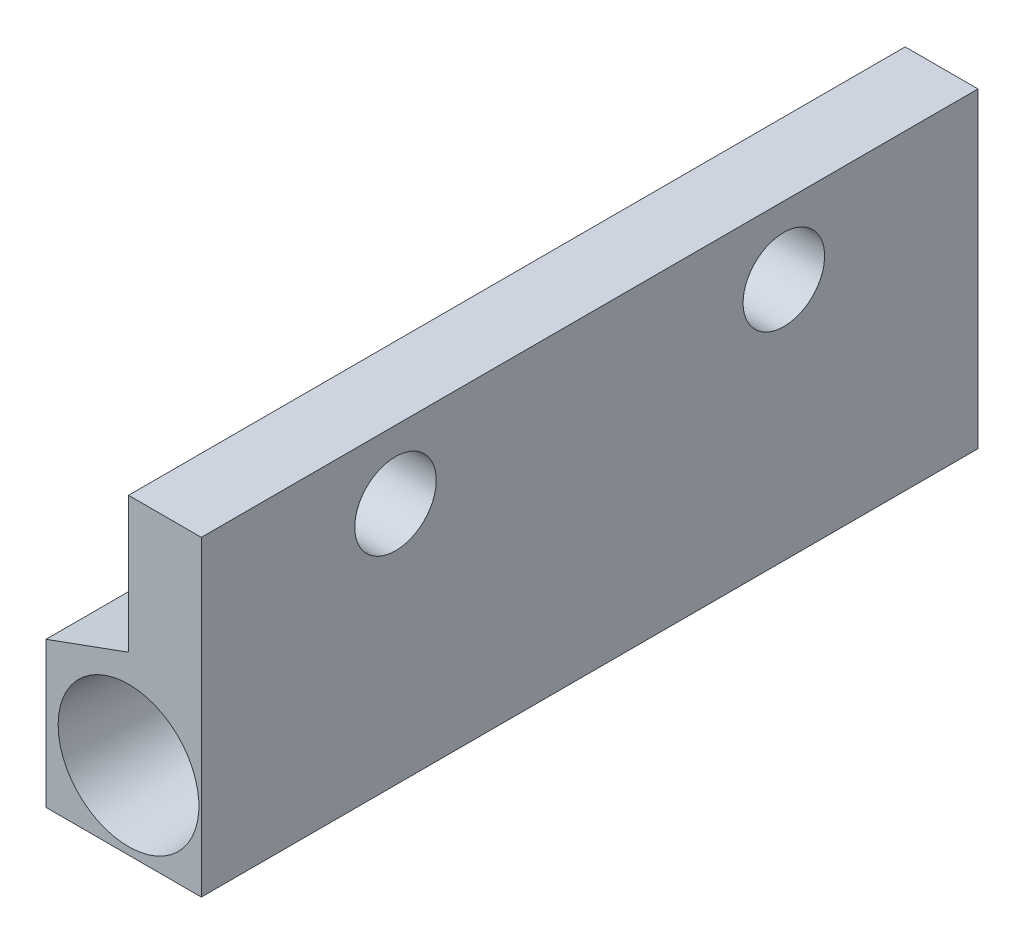
SolidWorks part; units mm, degrees
material "PET"
ref_plane "Front Plane" through (0, 0, 0) normal (0, 0, 1) x (1, 0, 0)
ref_plane "Top Plane" through (0, 0, 0) normal (0, 1, 0) x (1, 0, 0)
ref_plane "Right Plane" through (0, 0, 0) normal (1, 0, 0) x (0, 0, -1)
sketch "Sketch1" plane through (0, 0, 0) normal (0, 0, 1) x (1, 0, 0)
  line L1 (-4.25, -4) -> (-4.25, 3.5)
  line L2 (-4.25, 3.5) -> (0, 5.0469)
  line L3 (0, 5.0469) -> (0, 12.0469)
  line L4 (0, 12.0469) -> (3.75, 12.0469)
  line L5 (3.75, 12.0469) -> (3.75, -4)
  line L8 (-4.25, -4) -> (3.75, -4)
  arc A0 (2.75, 0) -> (-2.75, 0) centre (0, 0) ccw
  arc A1 (-2.75, 0) -> (2.75, 0) centre (0, 0) ccw
  dimension "D1" = 5.5
  dimension "D7" = 3.5
  dimension "D2" = 3.75
  dimension "D3" = 4
  dimension "D4" = 110
  dimension "D5" = 8
  dimension "D6" = 7
extrude "Boss-Extrude1" add sketch "Sketch1" along normal blind 40
sketch "Sketch2" plane through (0, 0, 0) normal (-1, 0, 0) x (0, 0, 1)
  line L0 (0, 8.5469) -> (40, 8.5469) construction
  line L1 (0, 12.0469) -> (0, 5.0469) construction
  line L2 (40, 12.0469) -> (40, 5.0469) construction
  circle A0 centre (10, 8.5469) radius 2.1
  circle A1 centre (30, 8.5469) radius 2.1
  dimension "D1" = 4.2
  dimension "D2" = 10
  dimension "D3" = 4.2
  dimension "D4" = 10
extrude "Cut-Extrude1" cut sketch "Sketch2" against normal through all
chamfer "Chamfer1" distance 10 angle 5 1 edges at (2.75, 0, 40) first distance on face at (2.75, 0, 0)
chamfer "Chamfer2" distance 10 angle 5 1 edges at (2.75, 0, 0) first distance on face at (-2.75, 0, 30)
